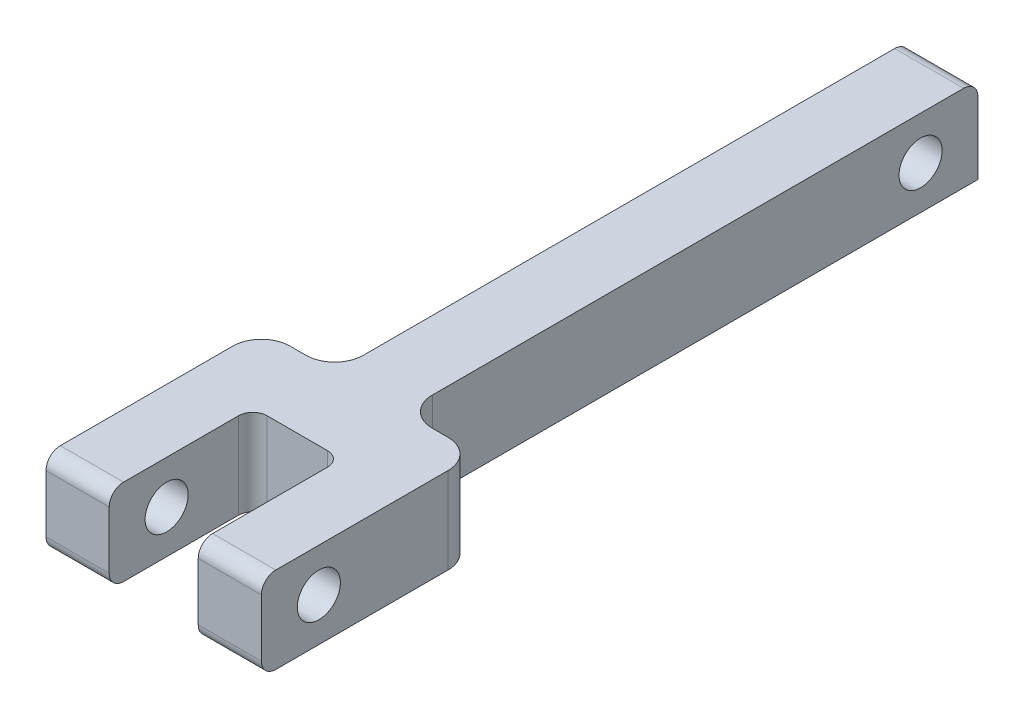
SolidWorks part; units mm, degrees
ref_plane "Alzado" through (0, 0, 0) normal (0, 0, 1) x (1, 0, 0)
ref_plane "Planta" through (0, 0, 0) normal (0, 1, 0) x (1, 0, 0)
ref_plane "Vista lateral" through (0, 0, 0) normal (1, 0, 0) x (0, 0, -1)
sketch "Croquis1" plane through (0, 0, 0) normal (1, 0, 0) x (0, 0, -1)
  line L0 (-26.5, 3) -> (26.5, 3)
  line L1 (26.5, -3) -> (27.5, -3)
  line L2 (-27.5, 0) -> (27.5, 0) construction
  line L3 (-27.5, 2) -> (-27.5, -2)
  line L4 (-26.5, -3) -> (26.5, -3)
  line L5 (27.5, 2) -> (27.5, -2)
  line L6 (27.5, -3) -> (27.5, -2)
  arc A0 (-27.5, -2) -> (-26.5, -3) centre (-26.5, -2) ccw
  arc A1 (-27.5, 2) -> (-26.5, 3) centre (-26.5, 2) cw
  arc A2 (26.5, -3) -> (27.5, -2) centre (26.5, -2) ccw construction
  arc A3 (26.5, 3) -> (27.5, 2) centre (26.5, 2) cw
  point P1 (0, 0)
  point P9 (-27.5, -3)
  point P13 (-27.5, 3)
  point P16 (27.5, -3)
  point P19 (27.5, 3)
  dimension "D3" = 1
  dimension "D4" = 1
  dimension "D1" = 3
  dimension "D2" = 55
extrude "Saliente-Extruir1" add sketch "Croquis1" along normal mid plane 4.8
sketch "Croquis2" plane through (0, 0, 0) normal (1, 0, 0) x (0, 0, -1)
  line L0 (-27.5, 2) -> (-27.5, -2) construction
  line L1 (27.5, -3) -> (27.5, 2) construction
  circle A0 centre (-23.5, 0) radius 1.5
  circle A1 centre (23.5, 0) radius 1.5
  dimension "D1" = 3
  dimension "D3" = 3
  dimension "D2" = 4
  dimension "D4" = 4
extrude "Cortar-Extruir1" cut sketch "Croquis2" against normal through all both and the other way through all
sketch "Croquis3" plane through (0, 0, 0) normal (1, 0, 0) x (0, 0, -1)
  line L0 (-27.5, 2) -> (-27.5, -2) construction
  line L1 (-27.5, 2) -> (-27.5, -2)
  line L2 (-26.5, 3) -> (-12.5, 3)
  line L3 (26.5, 3) -> (-26.5, 3) construction
  line L4 (-12.5, 3) -> (-12.5, -3)
  line L5 (-26.5, -3) -> (27.5, -3) construction
  line L6 (-12.5, -3) -> (-26.5, -3)
  circle A0 centre (-23.5, 0) radius 1.5 construction
  circle A1 centre (-23.5, 0) radius 1.5
  arc A2 (-26.5, 3) -> (-27.5, 2) centre (-26.5, 2) ccw construction
  arc A3 (-26.5, 3) -> (-27.5, 2) centre (-26.5, 2) ccw
  arc A4 (-27.5, -2) -> (-26.5, -3) centre (-26.5, -2) ccw construction
  arc A5 (-27.5, -2) -> (-26.5, -3) centre (-26.5, -2) ccw
  dimension "D1" = 15
extrude "Saliente-Extruir2" add sketch "Croquis3" along normal mid plane 15
sketch "Croquis4" plane through (0, 0, 0) normal (1, 0, 0) x (0, 0, -1)
  line L0 (-26.5, 3) -> (-17.5, 3)
  line L1 (-12.5, 3) -> (-26.5, 3) construction
  line L2 (-17.5, 3) -> (-17.5, -3)
  line L3 (-26.5, -3) -> (-12.5, -3) construction
  line L4 (-27.5, 2) -> (-27.5, -2)
  line L5 (-26.5, -3) -> (-12.5, -3)
  line L6 (-12.5, -3) -> (-12.5, 3)
  line L7 (-12.5, 3) -> (-26.5, 3)
  line L8 (-27.5, 2) -> (-27.5, -2)
  line L12 (-17.5, -3) -> (-26.5, -3)
  arc A2 (-26.5, 3) -> (-27.5, 2) centre (-26.5, 2) ccw
  arc A3 (-27.5, -2) -> (-26.5, -3) centre (-26.5, -2) ccw
  arc A4 (-26.5, 3) -> (-27.5, 2) centre (-26.5, 2) ccw
  arc A5 (-27.5, -2) -> (-26.5, -3) centre (-26.5, -2) ccw
  dimension "D2" = 10
  dimension "D1" = 0
extrude "Cortar-Extruir2" cut sketch "Croquis4" against normal mid plane 6.2
fillet "Redondeo1" radius 2 4 edges at (2.4, 0, 12.5) (-2.4, 0, 12.5) (7.5, 0, 12.5) (-7.5, 0, 12.5)
fillet "Redondeo2" radius 1 2 edges at (3.1, 0, 17.5) (-3.1, 0, 17.5)
